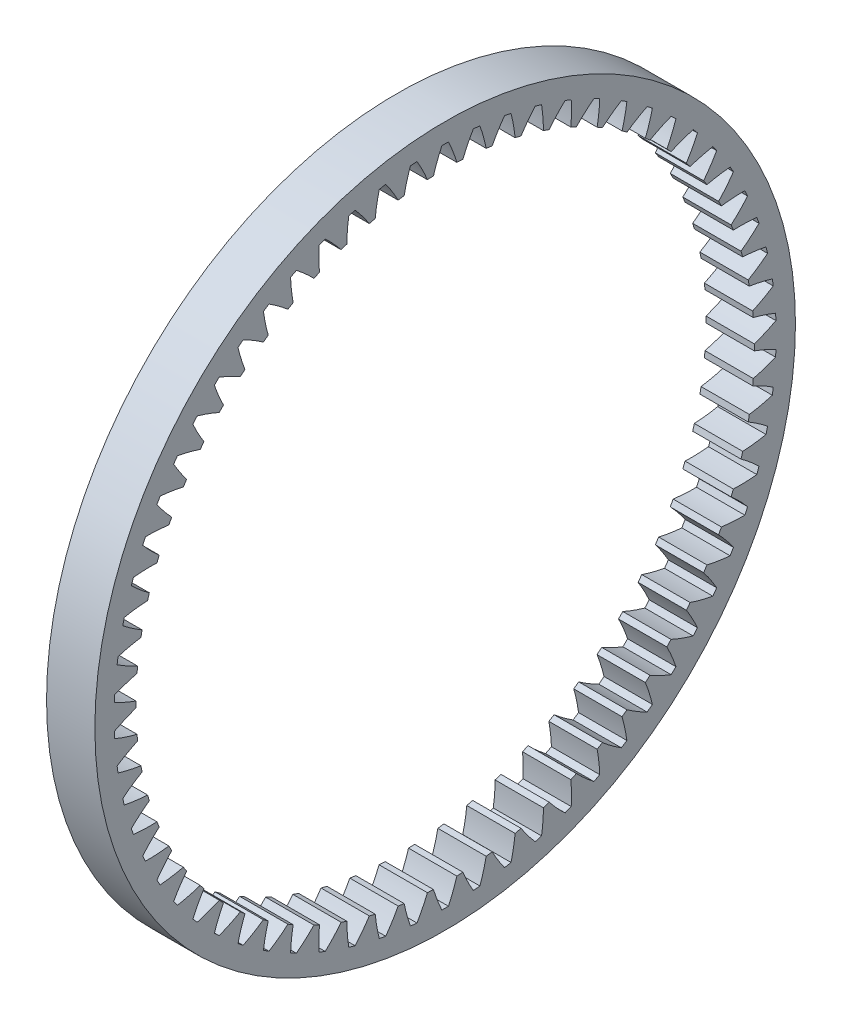
SolidWorks part; units mm, degrees
ref_plane "Plane1" through (0, 0, 0) normal (0, 0, 1) x (1, 0, 0)
ref_plane "Plane2" through (0, 0, 0) normal (0, 1, 0) x (1, 0, 0)
ref_plane "Plane3" through (0, 0, 0) normal (1, 0, 0) x (0, 0, -1)
sketch "HoldingSke" plane through (0, 0, 0) normal (0, 1, 0) x (1, 0, 0)
  line L0 (0, 0) -> (0.2034, -0.4568)
  line L1 (-15, 0) -> (100, 0) construction
  line L2 (0, 0) -> (-2.1039, 2.3779)
  line L3 (0, 0) -> (-11.863, 4.5341)
  line L4 (0, 0) -> (3.5126, 7.8894)
  line L5 (0, 0) -> (-23.7986, -8.8762)
  line L6 (0, 0) -> (-10.5278, -7.1032)
  line L7 (-2.1039, 2.3779) -> (3.3635, 27.1825)
  line L8 (-76.2, 4.3779) -> (-54.61, 4.3779)
  line L9 (-71.009, 38.7566) -> (-53.1078, 45.2721)
  line L10 (-76.2, 71.12) -> (104.1128, 71.12)
  line L11 (0, 0) -> (-10, 0)
  line L12 (-76.2, 101.6) -> (-76.133, 101.6)
  line L13 (24.9733, 27.94) -> (52.9518, 28.4284)
  line L14 (24.9733, 27.94) -> (24.9743, 27.94)
  line L15 (24.9733, 27.94) -> (100.4006, 29.5858)
  circle A0 centre (0, 0) radius 72.5
  circle A1 centre (0, 0) radius 12.7
  circle A2 centre (0, 0) radius 12.7
  dimension "Num_teeth" = 66
  dimension "Pitch_radius" = 180.3128
  dimension "Width" = 10
  dimension "Diameter" = 145
sketch "BasProSke" plane through (0, 0, 0) normal (0, 1, 0) x (1, 0, 0)
  line L0 (-10, 0) -> (60, 0) construction
  line L1 (0, 64) -> (0, 72.5)
  line L2 (0, 64) -> (10, 64)
  line L3 (10, 64) -> (10, 72.5)
  line L4 (10, 72.5) -> (0, 72.5)
  dimension "Thickness" = 10
  dimension "Diameter" = 145
revolve "Base-Revolve" add sketch "BasProSke" angle 360 about L0
sketch "TooCutSke" plane through (0, 0, 0) normal (1, 0, 0) x (0, 0, -1)
  line L3 (1.7381, 65.9771) -> (1.7381, 53.6633) construction
  line L4 (0, 0) -> (0, 59.563) construction
  line L5 (0, 0) -> (-3.2512, 68.2501) construction
  line L6 (-29.1981, 54.4902) -> (35.144, 57.5552) construction
  circle A0 centre (0, 0) radius 66 construction
  circle A1 centre (0, 0) radius 68.501 construction
  circle A2 centre (0, 0) radius 55.8177 construction
  circle A3 centre (0, 0) radius 63.9746 construction
  arc A4 (2.4233, 63.9287) -> (0.6815, 68.4976) centre (-29.1981, 54.4902) ccw
  arc A5 (2.4233, 63.9287) -> (-2.4233, 63.9287) centre (0, 0) ccw
  arc A6 (0.6815, 68.4976) -> (-0.6815, 68.4976) centre (0, 0) ccw
  arc A7 (-0.6815, 68.4976) -> (-2.4233, 63.9287) centre (29.1981, 54.4902) ccw
extrude "ToothCut" cut sketch "TooCutSke" along normal through all
fillet "Breaks" [suppressed] radius 0.2
fillet "RootFillets" [suppressed] radius 0.501
pattern_circular "TeethCuts" count 66 every 5.455 about axis through (-10, 0, 0) along (1, 0, 0) of "RootFillets", "Breaks", "ToothCut"
equation "' \"Module@HoldingSke\" = 6.35"
equation "' \"Num_teeth@HoldingSke\" = 24"
equation "' \"Ap@HoldingSke\" =  14.5"
equation "' \"Ap@HoldingSke\" = 14.5"
equation "' \"Width@HoldingSke\" = 12"
equation "' \"Diameter@HoldingSke\" = 8 * 25.4"
equation "' \"Show_teeth@HoldingSke\" = 100"
equation "' \"Backlash@HoldingSke\" = 0.009 * 25.4"
equation "' \"Addendum_fac@HoldingSke\" = 1.0"
equation "' \"Dedendum_fac@HoldingSke\" = 1.25"
equation "' \"Dedendum_add@HoldingSke\" = 0.00005 * 25.4"
equation "' \"Clearance_fac@HoldingSke\" = 0.25"
equation "\"Pitch@HoldingSke\" = 1 / \"Module@HoldingSke\" "
equation "\"Overcut_dia@TooCutSke\" = (\"Num_teeth@HoldingSke\" - 2 * \"Addendum_fac@HoldingSke\") / \"Pitch@HoldingSke\" - 0.002 * 25.4"
equation "\"Pitch_dia@TooCutSke\" = \"Num_teeth@HoldingSke\" / \"Pitch@HoldingSke\""
equation "\"Base_dia@TooCutSke\" = \"Num_teeth@HoldingSke\" / \"Pitch@HoldingSke\" * cos((\"Ap@HoldingSke\"  * 3.14159265 / 180)) * 0.90"
equation "\"Root_dia@TooCutSke\" = \"Num_teeth@HoldingSke\"  / \"Pitch@HoldingSke\" + 2 *  \"Dedendum_fac@HoldingSke\"/ \"Pitch@HoldingSke\" + \"Dedendum_add@HoldingSke\" * 2"
equation "\"Half_ang@TooCutSke\" = 180 / \"Num_teeth@HoldingSke\""
equation "\"Half_CT@TooCutSke\" = \"Num_teeth@HoldingSke\" / \"Pitch@HoldingSke\" * sin((3.14159265 / 2 / \"Num_teeth@HoldingSke\")) / 2 + 10 * \"Backlash@HoldingSke\" / 4"
equation "\"Flank_rad@TooCutSke\" = \"Num_teeth@HoldingSke\" / \"Pitch@HoldingSke\" / 4"
equation "\"Radius@RootFillets\"= \"Clearance_fac@HoldingSke\" / \"Pitch@HoldingSke\" + \"Dedendum_add@HoldingSke\""
equation "\"Break_rad@Breaks\" = 0.02 / \"Pitch@HoldingSke\" * 5"
equation "\"Num_teeth@TeethCuts\" = int( \"Show_teeth@HoldingSke\" ) + 1"
equation "\"Num_teeth@TeethCuts\" = ((sgn( \"Num_teeth@TeethCuts\" - \"Num_teeth@HoldingSke\" )-1)*( \"Num_teeth@TeethCuts\" - \"Num_teeth@HoldingSke\" ))/-2+ \"Num_teeth@HoldingSke\""
equation "\"Num_teeth@TeethCuts\" = ((sgn( \"Num_teeth@TeethCuts\" - 2.0)+1)*( \"Num_teeth@TeethCuts\" - 2.0))/2 +2.0"
equation "\"Angle@TeethCuts\" = 360.0 / \"Num_teeth@HoldingSke\""
equation "\"Diameter@BasProSke\" = \"Num_teeth@HoldingSke\"  / \"Pitch@HoldingSke\" + 2 *  \"Dedendum_fac@HoldingSke\"/ \"Pitch@HoldingSke\" + \"Dedendum_add@HoldingSke\" * 2 + 0.002 * 25.4"
equation "\"Diameter@BasProSke\" = ((sgn( \"Diameter@BasProSke\"  - \"Diameter@HoldingSke\" )+1)*( \"Diameter@BasProSke\"  - \"Diameter@HoldingSke\" ))/2 + \"Diameter@HoldingSke\""
equation "\"Inside_diameter@BasProSke\" =  (\"Num_teeth@HoldingSke\" - 2 * \"Addendum_fac@HoldingSke\") / \"Pitch@HoldingSke\" "
equation "\"Thickness@BasProSke\"  = \"Width@HoldingSke\""
